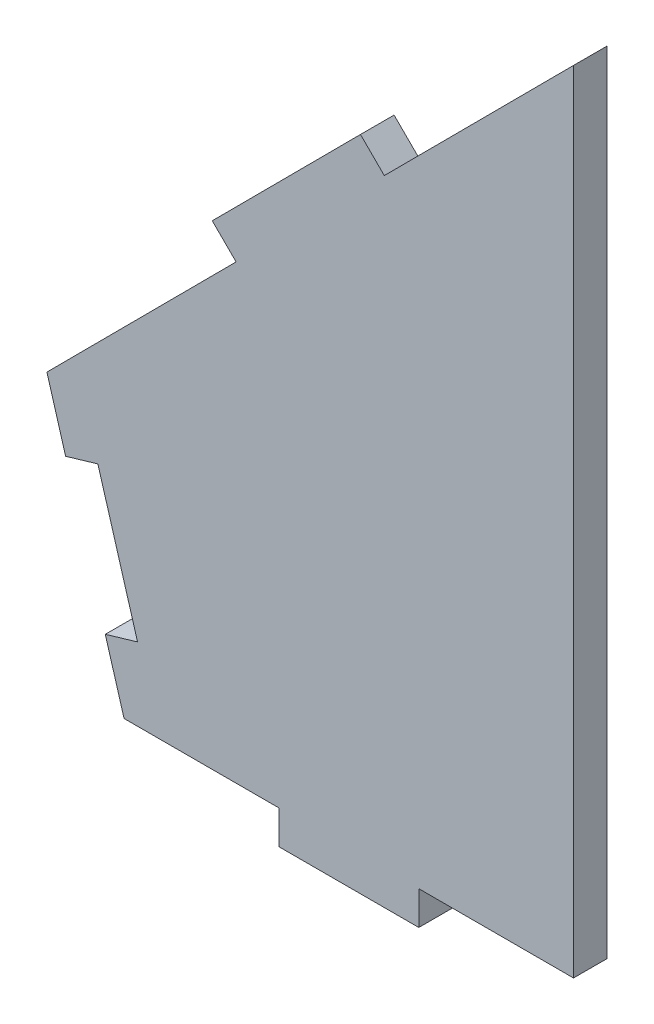
SolidWorks part; units mm, degrees
ref_plane "Front Plane" through (0, 0, 0) normal (0, 0, 1) x (1, 0, 0)
ref_plane "Top Plane" through (0, 0, 0) normal (0, 1, 0) x (1, 0, 0)
ref_plane "Right Plane" through (0, 0, 0) normal (1, 0, 0) x (0, 0, -1)
sketch "Sketch1" plane through (0, 0, 0) normal (0, 0, 1) x (1, 0, 0)
  line L0 (-16.8229, 31.0188) -> (-25.4011, 22.4034)
  line L1 (0, 30.3874) -> (0, 19.4332)
  line L2 (0, 19.4332) -> (-1.524, 19.4332)
  line L3 (-1.524, 19.4332) -> (-1.524, 46.3839)
  line L4 (-10.1023, 37.7685) -> (-11.1822, 38.8438)
  line L5 (-16.8229, 31.0188) -> (-17.9028, 32.0941)
  line L6 (-1.524, 46.3839) -> (-10.1023, 37.7685)
  line L7 (-25.4011, 22.4034) -> (-24.5505, 19.522)
  line L8 (-22.7526, 13.4318) -> (-21.902, 10.5505)
  line L9 (-11.1822, 38.8438) -> (-17.9028, 32.0941)
  line L10 (-22.7526, 13.4318) -> (-21.291, 13.8633)
  line L11 (-21.902, 10.5505) -> (-14.888, 10.5505)
  line L12 (-24.5505, 19.522) -> (-23.0889, 19.9535)
  line L14 (-1.524, -4.5575) -> (-1.524, 54.3782) construction
  line L15 (18.3147, 24.1558) -> (19.673, 24.5832)
  line L16 (18.3147, 24.1558) -> (19.673, 24.5832)
  line L17 (17.3998, 27.0633) -> (18.7581, 27.4907)
  line L18 (17.3998, 27.0633) -> (18.7581, 27.4907)
  line L19 (-1.524, 10.5505) -> (-1.524, 19.4332)
  line L20 (-8.538, 10.5505) -> (-1.524, 10.5505)
  line L21 (-21.291, 13.8633) -> (-23.0889, 19.9535)
  line L22 (-14.888, 10.5505) -> (-14.888, 9.0265)
  line L23 (-8.538, 10.5505) -> (-8.538, 9.0265)
  line L25 (-14.888, 9.0265) -> (-8.538, 9.0265)
  line L35 (0, 30.3874) -> (-1.524, 19.4332)
  dimension "D1" = 1.524
  dimension "D2" = 1.524
extrude "Boss-Extrude1" add sketch "Sketch1" along normal blind 1.524 contours L35 L1 L2 L3 L6 L4 L9 L5 L0 L7 L12 L21 L10 L8 L11 L22 L25 L23 L20 L19 region at (-10.8638, 23.9842, 0)
